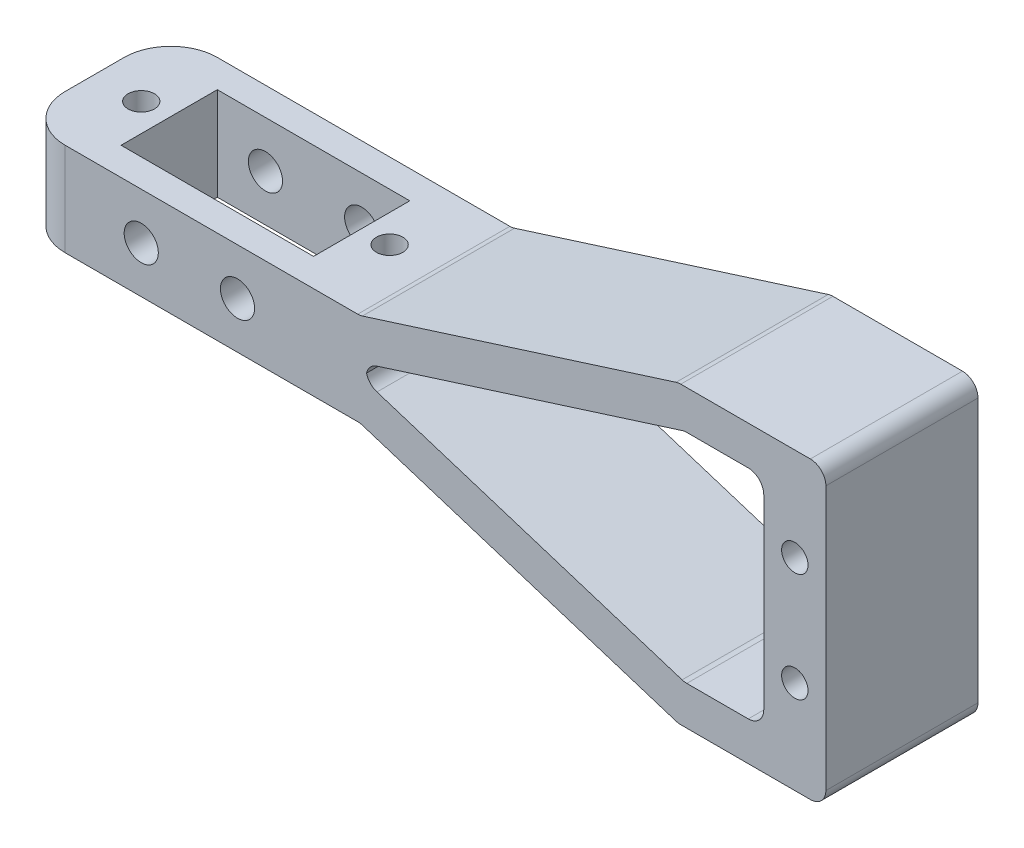
SolidWorks part; units mm, degrees
material "ABS"
ref_plane "前视基准面" through (0, 0, 0) normal (0, 0, 1) x (1, 0, 0)
ref_plane "上视基准面" through (0, 0, 0) normal (0, 1, 0) x (1, 0, 0)
ref_plane "右视基准面" through (0, 0, 0) normal (1, 0, 0) x (0, 0, -1)
sketch "草图1" plane through (0, 0, 0) normal (0, 0, 1) x (1, 0, 0)
  line L1 (-22, -6) -> (22, -6)
  line L2 (-22, -6) -> (-22, 6)
  line L3 (-22, 6) -> (22, 6)
  line L4 (22, -6) -> (22, 6) construction
  line L5 (-22, -6) -> (22, 6) construction
  line L6 (-22, 6) -> (22, -6) construction
  line L8 (63, -19) -> (22, -6)
  line L9 (63, 19) -> (82, 19)
  line L10 (22, 6) -> (63, 19)
  line L11 (-6.2, 0) -> (6.2, 0) construction
  line L12 (82, 19) -> (82, -19)
  line L13 (82, -19) -> (63, -19)
  line L14 (22, 0) -> (82, 0) construction
  circle A2 centre (-6.2, 0) radius 2.2
  circle A3 centre (6.2, 0) radius 2.2
  circle A4 centre (78, 7) radius 1.7
  circle A6 centre (78, -7) radius 1.7
  point P0 (0, 0)
  dimension "D3" = 4.4
  dimension "D4" = 4.4
  dimension "D10" = 3.4
  dimension "D11" = 4
  dimension "D12" = 7
  dimension "D13" = 3.4
  dimension "D14" = 4
  dimension "D15" = 7
  dimension "D1" = 12
  dimension "D2" = 12.4
  dimension "D5" = 44
  dimension "D6" = 104
  dimension "D7" = 19
  dimension "D8" = 19
  dimension "D9" = 38
extrude "凸台-拉伸1" add sketch "草图1" along normal blind 19.6
sketch "草图2" plane through (0, 6, 0) normal (0, 1, 0) x (1, 0, 0)
  line L0 (0, 0) -> (0, -9.8) construction
  line L1 (-12.4, -16) -> (12.4, -16)
  line L2 (-12.4, -16) -> (-12.4, -3.6)
  line L3 (-12.4, -3.6) -> (12.4, -3.6)
  line L4 (12.4, -16) -> (12.4, -3.6)
  line L5 (-12.4, -16) -> (12.4, -3.6) construction
  line L6 (-12.4, -3.6) -> (12.4, -16) construction
  line L7 (0, -9.8) -> (22, -9.8) construction
  line L8 (22, -19.6) -> (22, 0) construction
  circle A0 centre (16, -9.8) radius 1.7
  circle A1 centre (-16, -9.8) radius 1.7
  point P0 (0, -9.8)
  dimension "D3" = 3.4
  dimension "D4" = 3.4
  dimension "D5" = 16
  dimension "D6" = 16
  dimension "D1" = 24.8
  dimension "D2" = 12.4
extrude "切除-拉伸1" cut sketch "草图2" against normal through all
sketch "草图3" plane through (0, 0, 19.6) normal (0, 0, 1) x (1, 0, 0)
  line L0 (74, 14) -> (74, -14)
  line L1 (74, -14) -> (63.7737, -14)
  line L2 (63.7737, -14) -> (22.7737, -1)
  line L3 (22.7737, -1) -> (22.7737, 1)
  line L4 (22.7737, 1) -> (63.7737, 14)
  line L5 (63.7737, 14) -> (74, 14)
  line L6 (82, -19) -> (82, 19) construction
  line L7 (82, 19) -> (63, 19) construction
  line L8 (63, -19) -> (82, -19) construction
  line L10 (63, 19) -> (22, 6) construction
  line L11 (22, -6) -> (63, -19) construction
  dimension "D1" = 8
  dimension "D2" = 5
  dimension "D3" = 5
  dimension "D4" = 5
  dimension "D5" = 5
  dimension "D6" = 2
extrude "切除-拉伸2" cut sketch "草图3" against normal through all
fillet "圆角1" radius 2 12 edges at (74, 14, 9.8) (63.7737, 14, 9.8) (74, -14, 9.8) (63.7737, -14, 9.8) (22.7737, 1, 9.8) (22.7737, -1, 9.8) (82, -19, 9.8) (82, 19, 9.8) (63, -19, 9.8) (22, -6, 9.8) (63, 19, 9.8) (22, 6, 9.8)
fillet "圆角2" radius 6 2 edges at (-22, 0, 0) (-22, 0, 19.6)
